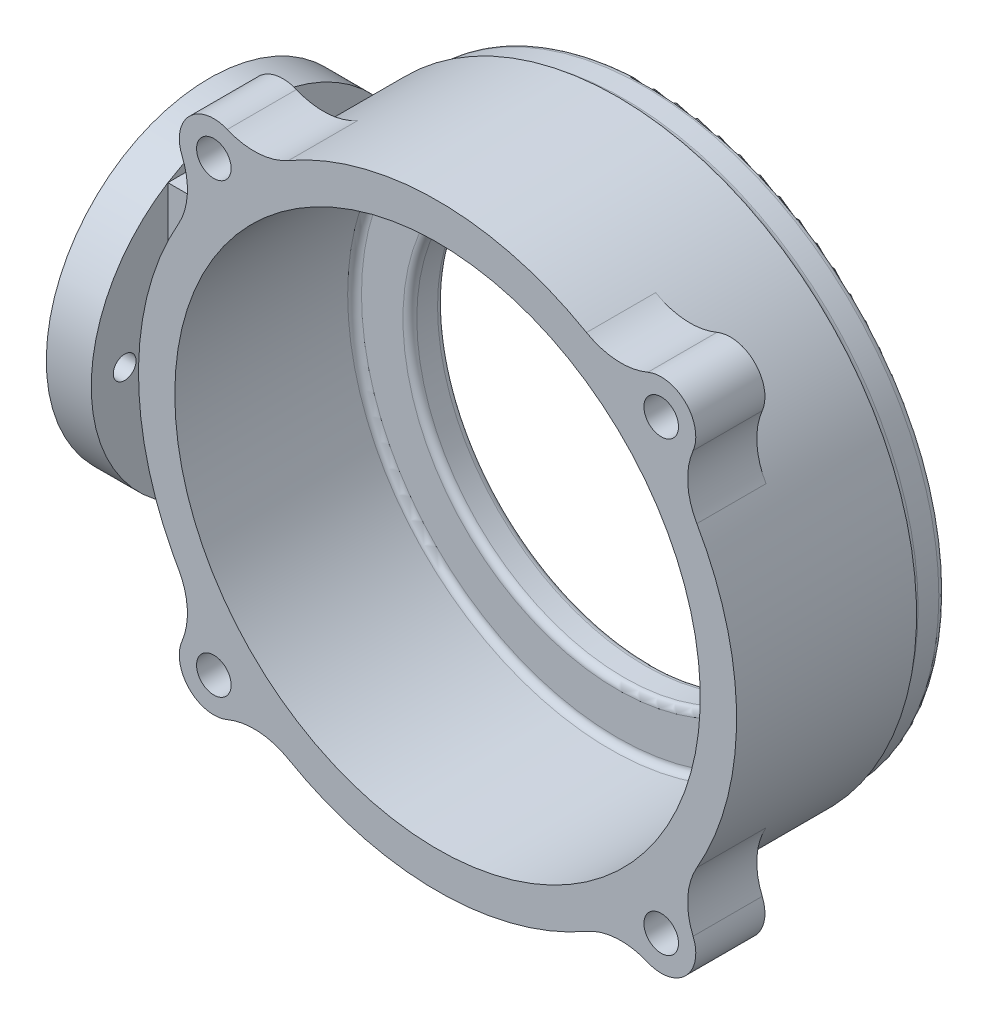
SolidWorks part; units mm, degrees
ref_plane "Front Plane" through (0, 0, 0) normal (0, 0, 1) x (1, 0, 0)
ref_plane "Top Plane" through (0, 0, 0) normal (0, 1, 0) x (1, 0, 0)
ref_plane "Right Plane" through (0, 0, 0) normal (1, 0, 0) x (0, 0, -1)
sketch "Sketch1" plane through (0, 0, 0) normal (0, 0, 1) x (1, 0, 0)
  line L0 (0, 0) -> (-45, 0) construction
  line L4 (0, 43.25) -> (-45, 43.25) construction
  line L5 (-45, 43.25) -> (-45, -43.25) construction
  line L6 (0, -43.25) -> (-45, -43.25) construction
  line L7 (-38.3479, 20) -> (-45, 20)
  line L8 (-45, 20) -> (-45, -20)
  line L9 (-38.3479, -20) -> (-45, -20)
  circle A0 centre (0, 0) radius 38
  arc A1 (0, -43.25) -> (0, 43.25) centre (0, 0) ccw construction
  arc A2 (-38.3479, -20) -> (-38.3479, 20) centre (0, 0) ccw
  dimension "D1" = 76
  dimension "D2" = 43.25
  dimension "D4" = 40
  dimension "D3" = 45
extrude "Boss-Extrude1" add sketch "Sketch1" along normal blind 40
sketch "Sketch6" plane through (0, 0, 0) normal (0, 0, -1) x (-1, 0, 0)
  circle A0 centre (0, 0) radius 99.6758
extrude "Cut-Extrude3" cut sketch "Sketch6" against normal mid plane 40
sketch "Sketch7" plane through (0, 0, 20) normal (0, 0, 1) x (1, 0, 0)
  circle A1 centre (0, 0) radius 42.5
  circle A2 centre (0, 0) radius 30
  dimension "D1" = 60
  dimension "D2" = 85
extrude "Boss-Extrude4" add sketch "Sketch7" against normal blind 5
fillet "Fillet1" radius 1 5 edges at (42.5, 0, 15) (30, 0, 15) (-38, 0, 20) (30, 0, 20) (42.5, 0, 20)
sketch "Sketch8" plane through (-45, 0, 0) normal (-1, 0, 0) x (0, 0, 1)
  line L0 (27.5, 0) -> (27.5, 18.75) construction
  line L7 (27.5, 0) -> (46.25, 0) construction
  line L10 (15, 0) -> (40, 0) construction
  line L11 (15, 41.5) -> (15, -41.5) construction
  line L12 (40, 0) -> (15, 0) construction
  line L13 (27.5, 0) -> (27.5, 43.25) construction
  line L14 (40, 20) -> (40, -20) construction
  arc A13 (22.5046, -0.2152) -> (22.504, -0.1987) centre (27.5, 0) ccw construction
  arc A14 (22.504, -0.1987) -> (22.5046, -0.2152) centre (27.5, 0) ccw construction
  arc A15 (25.8502, 18.7248) -> (25.8502, 18.7215) centre (27.5, 18.75) ccw construction
  circle A31 centre (27.5, 18.75) radius 1.65
  circle A32 centre (27.5, 0) radius 5
  circle A33 centre (46.25, 0) radius 1.65
  circle A34 centre (27.5, -18.75) radius 1.65
  circle A35 centre (8.75, 0) radius 1.65
  circle A37 centre (27.5, 0) radius 23.585
  point P7 (30.3176, 0)
  point P9 (0, 0)
  point P26 (0, 0)
  point P29 (27.5, 0)
  point P37 (-17.5, 0)
  dimension "D5" = 18.75
  dimension "D4" = 3.3
  dimension "D6" = 10
  dimension "D7" = 4
extrude "Boss-Extrude5" add sketch "Sketch8" along normal blind 6.5
ref_axis "Axis1" through (0, 0, 40) along (0, 0, -1)
sketch "Sketch9" plane through (0, 0, 0) normal (0, 1, 0) x (1, 0, 0)
  line L0 (0, -40) -> (0, -46) construction
  line L1 (0, -40) -> (0, -21) construction
  line L2 (0, -46) -> (42.5, -46) construction
  line L3 (42.5, -46) -> (42.5, -17.5) construction
  line L4 (42.5, -19) -> (42.5, -16) construction
  line L9 (-38.3479, -40) -> (43.25, -40) construction
  line L10 (38, -40) -> (38, -46)
  line L11 (43.25, -40) -> (43.25, -19.9682) construction
  line L12 (38, -40) -> (43.25, -40)
  line L14 (43.25, -40) -> (43.25, -46)
  line L15 (43.25, -46) -> (42.5, -46)
  line L17 (42.5, -46) -> (38, -46)
  point P12 (0, 0)
  point P21 (0, 0)
  dimension "D1" = 5.25
  dimension "D2" = 6
revolve "Revolve1" add sketch "Sketch9" angle 360 about L0
sketch "Sketch10" plane through (0, 0, 46) normal (0, 0, 1) x (1, 0, 0)
  line L0 (0, 0) -> (-32.3501, 32.3501) construction
  line L1 (-38.3479, 20) -> (-45, 20) construction
  line L2 (0, 0) -> (32.3501, 32.3501) construction
  line L3 (0, 0) -> (32.3501, -32.3501) construction
  line L4 (0, 0) -> (-32.3501, -32.3501) construction
  circle A2 centre (-32.3501, 32.3501) radius 2.5
  circle A3 centre (0, 0) radius 43.25 construction
  arc A7 (-27.3533, 32.5276) -> (-32.5276, 27.3533) centre (-32.3501, 32.3501) ccw
  arc A10 (-27.3533, 32.5276) -> (-32.5276, 27.3533) centre (0, 0) ccw
  circle A11 centre (32.3501, 32.3501) radius 2.5 [skipped]
  circle A12 centre (32.3501, -32.3501) radius 2.5 [skipped]
  circle A13 centre (-32.3501, -32.3501) radius 2.5 [skipped]
  circle A15 centre (32.3501, 32.3501) radius 2.5
  arc A16 (32.5276, 27.3533) -> (27.3533, 32.5276) centre (32.3501, 32.3501) ccw
  arc A17 (32.5276, 27.3533) -> (27.3533, 32.5276) centre (0, 0) ccw
  circle A18 centre (32.3501, -32.3501) radius 2.5
  arc A19 (27.3533, -32.5276) -> (32.5276, -27.3533) centre (32.3501, -32.3501) ccw
  arc A20 (27.3533, -32.5276) -> (32.5276, -27.3533) centre (0, 0) ccw
  circle A21 centre (-32.3501, -32.3501) radius 2.5
  arc A22 (-32.5276, -27.3533) -> (-27.3533, -32.5276) centre (-32.3501, -32.3501) ccw
  arc A23 (-32.5276, -27.3533) -> (-27.3533, -32.5276) centre (0, 0) ccw
  point P18 (0, 0)
  point P35 (0, 0)
  dimension "D1" = 45
  dimension "D2" = 5
  dimension "D4" = 10
  dimension "D6" = 42.5
  dimension "D3" = 4
  dimension "D5" = 4
extrude "Boss-Extrude6" add sketch "Sketch10" against normal blind 10
fillet "Fillet2" radius 10 8 edges at (-27.464, 33.411, 41) (-33.411, 27.464, 41) (27.464, 33.411, 41) (33.411, 27.464, 41) (-33.411, -27.464, 41) (-27.464, -33.411, 41) (27.464, -33.411, 41) (33.411, -27.464, 41)
